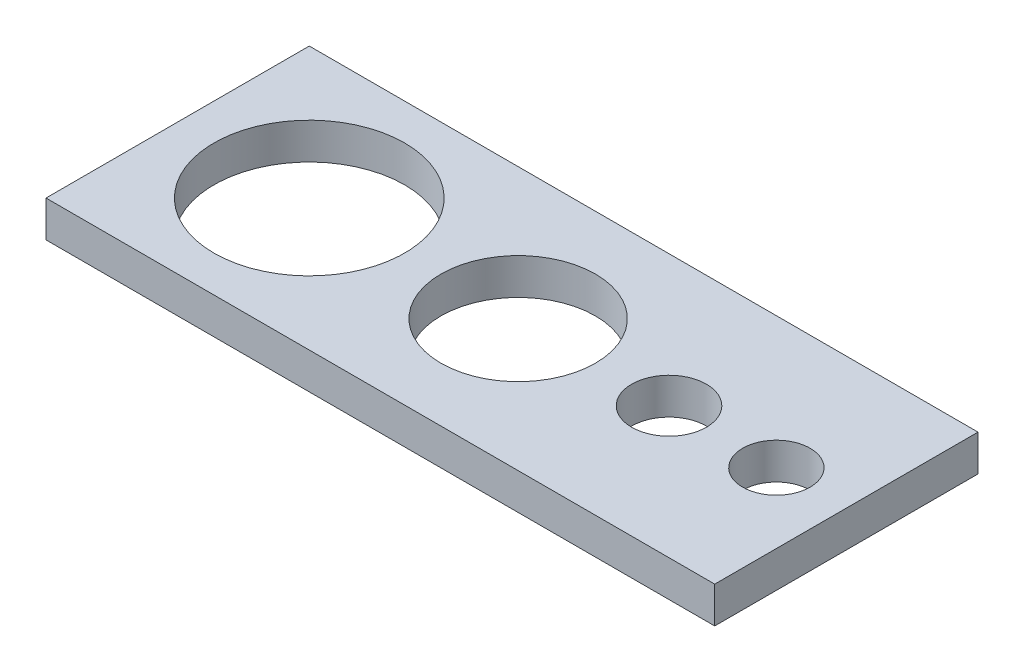
SolidWorks part; units mm, degrees
ref_plane "Спереди" through (0, 0, 0) normal (0, 0, 1) x (1, 0, 0)
ref_plane "Сверху" through (0, 0, 0) normal (0, 1, 0) x (1, 0, 0)
ref_plane "Справа" through (0, 0, 0) normal (1, 0, 0) x (0, 0, -1)
sketch "Эскиз1" plane through (0, 0, 0) normal (0, 1, 0) x (1, 0, 0)
  line L0 (0, 0) -> (5, 0) construction
  line L1 (31.3, 0) -> (36.3, 0) construction
  line L2 (57.6, 0) -> (62.6, 0) construction
  line L3 (72.9, 0) -> (77.9, 0) construction
  line L4 (87.2, 0) -> (92.2, 0) construction
  line L5 (18.15, 13.15) -> (18.15, 18.15) construction
  line L6 (18.15, -13.15) -> (18.15, -18.15) construction
  line L7 (0, 0) -> (0, 18.15)
  line L8 (0, 18.15) -> (92.2, 18.15)
  line L9 (92.2, 18.15) -> (92.2, -18.15)
  line L10 (92.2, -18.15) -> (0, -18.15)
  line L11 (0, -18.15) -> (0, 0)
  circle A0 centre (18.15, 0) radius 13.15
  circle A1 centre (46.95, 0) radius 10.65
  circle A2 centre (67.75, 0) radius 5.15
  circle A3 centre (82.55, 0) radius 4.65
  dimension "D1" = 26.3
  dimension "D2" = 21.3
  dimension "D3" = 10.3
  dimension "D4" = 9.3
  dimension "D5" = 5
extrude "Бобышка-Вытянуть1" add sketch "Эскиз1" along normal blind 5
